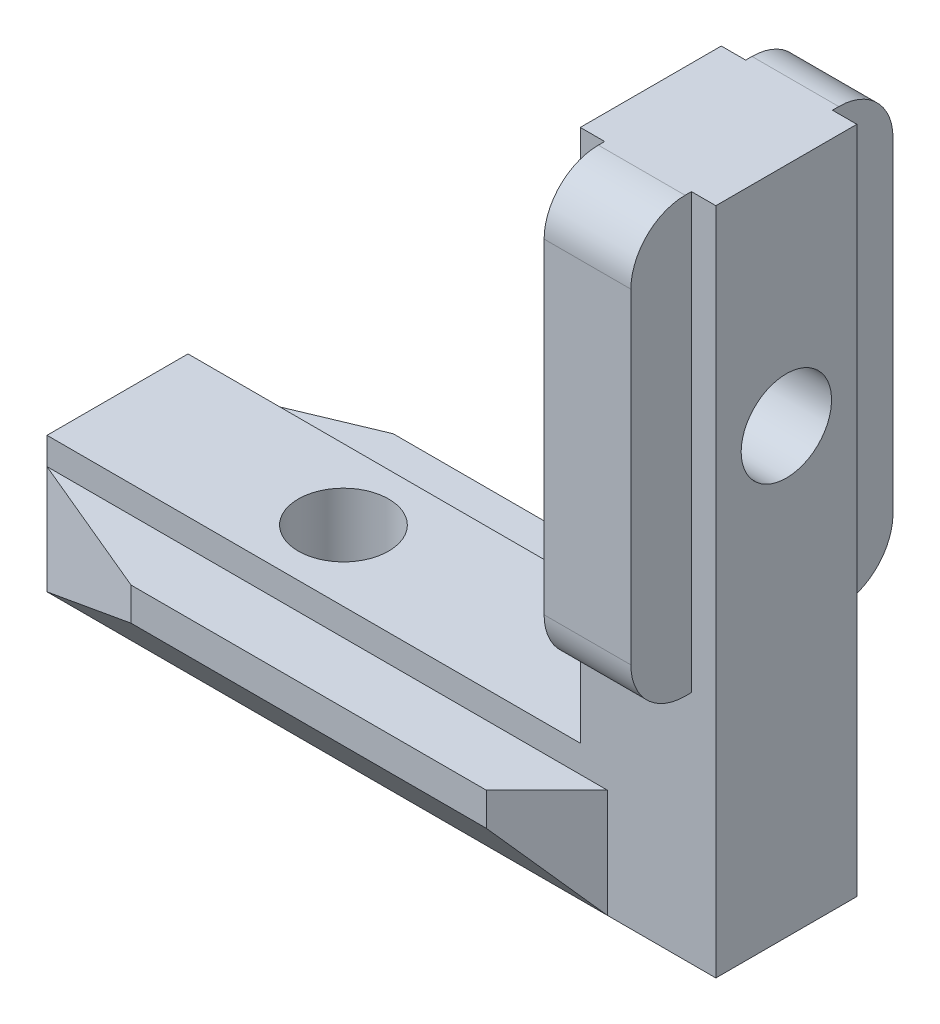
SolidWorks part; units mm, degrees
ref_plane "前视基准面" through (0, 0, 0) normal (0, 0, 1) x (1, 0, 0)
ref_plane "上视基准面" through (0, 0, 0) normal (0, 1, 0) x (1, 0, 0)
ref_plane "右视基准面" through (0, 0, 0) normal (1, 0, 0) x (0, 0, -1)
sketch "草图1" plane through (0, 0, 0) normal (0, 0, 1) x (1, 0, 0)
  line B0 (-37, 0) -> (0, 0)
  line B1 (0, 0) -> (0, 37)
  line B2 (-37, 7.5) -> (-7.5, 7.5)
  line B3 (-7.5, 7.5) -> (-7.5, 37)
  line B4 (-37, 7.5) -> (-37, 0)
  line B5 (-7.5, 37) -> (0, 37)
sketch_block_instance "A$C54BC447A-1"
sketch_block "A$C54BC447A"
extrude "凸台-拉伸1" add sketch "草图1" along normal mid plane 7.8
sketch "草图3" plane through (-37, 0, 0) normal (-1, 0, 0) x (0, 0, 1)
  line L0 (-3.9, 0) -> (-7.25, 4.1744)
  line L1 (-7.25, 4.1744) -> (-7.25, 6)
  line L2 (-7.25, 6) -> (-3.9, 6)
  line L3 (-3.9, 7.5) -> (-3.9, 0) construction
  line L4 (-3.9, 6) -> (-3.9, 0)
  line L5 (3.9, 7.5) -> (-3.9, 7.5) construction
  line L6 (0, 0) -> (0, 10.1809) construction
  line L7 (3.9, 6) -> (3.9, 0)
  line L8 (7.25, 6) -> (3.9, 6)
  line L9 (7.25, 4.1744) -> (7.25, 6)
  line L10 (3.9, 0) -> (7.25, 4.1744)
  dimension "D1" = 1.5
  dimension "D3" = 3.35
extrude "凸台-拉伸2" add sketch "草图3" against normal blind 35.65
chamfer "倒角1" distance 8 distance2 3.35 2 edges at (-37, 5.0872, -7.25) (-37, 5.0872, 7.25) first distance on face at (-19.175, 5.0872, -7.25) first distance on face at (-19.175, 5.0872, 7.25)
chamfer "倒角2" distance 8 angle 45 2 edges at (-1.35, 5.0872, 7.25) (-1.35, 5.0872, -7.25)
ref_plane "基准面2" through (-3.75, 0, 0) normal (-1, 0, 0) x (0, 0, 1)
sketch "草图4" plane through (-3.75, 0, 0) normal (-1, 0, 0) x (0, 0, 1)
  line L0 (-3.9, 37) -> (-4.25, 37)
  line L1 (-7.25, 16) -> (-7.25, 34)
  line L2 (-4.25, 13) -> (-3.9, 13)
  line L3 (-7.25, 6) -> (-3.9, 6) construction
  line L5 (-3.9, 37) -> (-3.9, 13)
  line L7 (0, 7.5) -> (0, 22.6136) construction
  line L8 (3.9, 7.5) -> (-3.9, 7.5) construction
  line L9 (3.9, 37) -> (3.9, 13)
  line L10 (4.25, 13) -> (3.9, 13)
  line L11 (7.25, 16) -> (7.25, 34)
  line L12 (3.9, 37) -> (4.25, 37)
  arc A0 (-4.25, 37) -> (-7.25, 34) centre (-4.25, 34) ccw
  arc A1 (-4.25, 13) -> (-7.25, 16) centre (-4.25, 16) cw
  arc A2 (4.25, 13) -> (7.25, 16) centre (4.25, 16) ccw
  arc A3 (4.25, 37) -> (7.25, 34) centre (4.25, 34) cw
  dimension "D2" = 3
  dimension "D1" = 7
extrude "凸台-拉伸3" add sketch "草图4" along normal mid plane 4.8
sketch "草图5" plane through (0, 7.5, 0) normal (0, 1, 0) x (1, 0, 0)
  line L0 (0, -3.9) -> (0, 3.9) construction
  point P0 (-24.5, 0)
  dimension "D1" = 24.5
hole_wizard "M6 螺纹孔1" positions "3D草图1" profile "草图6" tap size "M6" standard "Iso"
sketch3d "3D草图1"
  point P0 (-24.5, 7.5, 0)
sketch "草图6" plane through (-24.5, 7.5, 0) normal (1, 0, 0) x (0, 0, 1)
  line L0 (0, 0) -> (0, 29.5022)
  line L1 (0, 29.5022) -> (2.5, 28)
  line L2 (2.5, 28) -> (2.5, 0)
  line L5 (2.5, 0) -> (0, 0)
  line L10 (0, 29.5022) -> (-2.5, 28) construction
  line L11 (0, -6.35) -> (0, 107.95) construction
  dimension "螺纹孔钻头直径" = 5
  dimension "螺纹孔钻头深度" = 28
  dimension "导头角度" = 118
cosmetic thread "孔螺蚊线1" parameters "D1"=7.5, "D2"=6
ref_plane "基准面3" through (0, 0, 0) normal (-0.7071, -0.7071, 0) x (-0.7071, 0.7071, 0)
mirror "镜向1" about plane through (0, 0, 0) normal (-0.7071, -0.7071, 0) of "M6 螺纹孔1"
